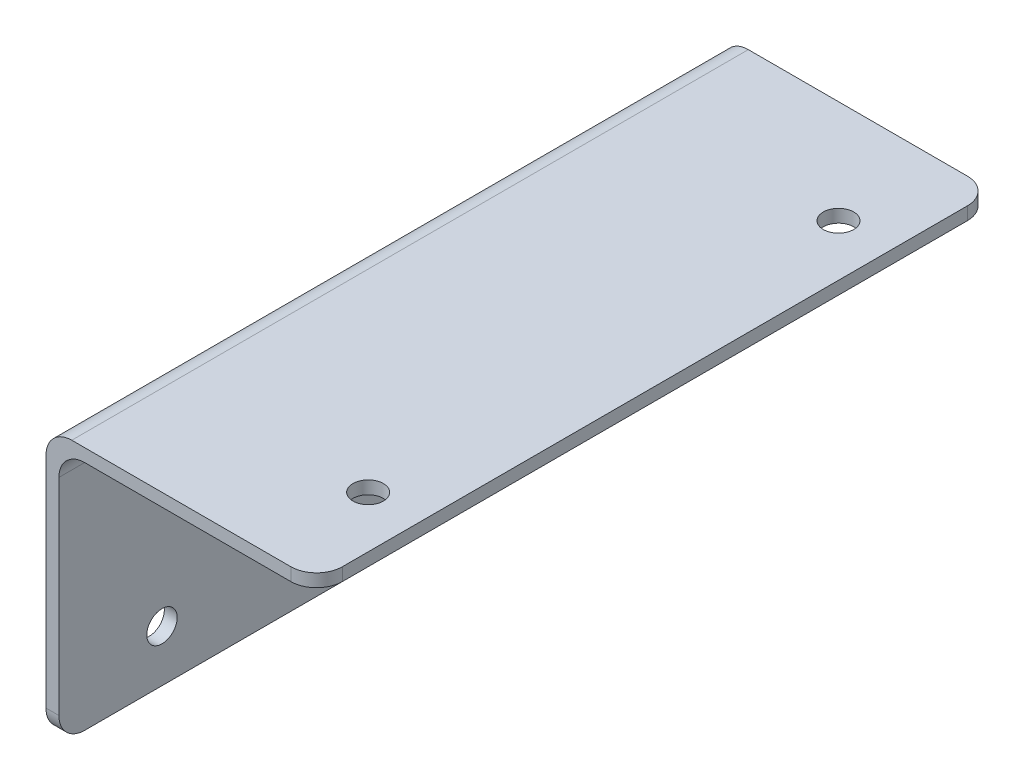
SolidWorks part; units mm, degrees
ref_plane "Front Plane" through (0, 0, 0) normal (0, 0, 1) x (1, 0, 0)
ref_plane "Top Plane" through (0, 0, 0) normal (0, 1, 0) x (1, 0, 0)
ref_plane "Right Plane" through (0, 0, 0) normal (1, 0, 0) x (0, 0, -1)
sketch "Sketch2" plane through (0, 0, 0) normal (0, 0, 1) x (1, 0, 0)
  line L1 (0, 0) -> (-1.27, 0)
  line L2 (0, 0) -> (0, 25.4)
  line L4 (-1.27, 0) -> (-1.27, 26.67)
  line L5 (-1.27, 26.67) -> (25.4, 26.67)
  line L7 (0, 25.4) -> (25.4, 25.4)
  line L8 (25.4, 26.67) -> (25.4, 25.4)
  dimension "D1" = 1.27
  dimension "D2" = 25.4
  dimension "D3" = 1.27
  dimension "D4" = 25.4
extrude "Boss-Extrude1" add sketch "Sketch2" along normal blind 66.675 contours L2 L7 L8 L5 L4 L1
sketch "Sketch3" plane through (-1.27, 0, 0) normal (-1, 0, 0) x (0, 0, 1)
  line L0 (33.3375, 0) -> (33.3375, 31.5293) construction
  line L1 (66.675, 0) -> (0, 0) construction
  circle A0 centre (10.16, 5.08) radius 1.5
  circle A1 centre (56.515, 5.08) radius 1.5
  dimension "D3" = 3
  dimension "D1" = 10.16
  dimension "D2" = 5.08
extrude "Cut-Extrude1" cut sketch "Sketch3" against normal through all
sketch "Sketch6" plane through (0, 26.67, 0) normal (0, 1, 0) x (1, 0, 0)
  line L0 (-1.27, -33.3375) -> (29.2999, -33.3375) construction
  line L1 (-1.27, -66.675) -> (-1.27, 0) construction
  circle A0 centre (20.32, -10.16) radius 1.5
  circle A1 centre (20.32, -56.515) radius 1.5
  dimension "D1" = 5.08
  dimension "D3" = 3
  dimension "D2" = 10.16
extrude "Cut-Extrude2" cut sketch "Sketch6" against normal through all
fillet "Fillet1" radius 2.54 4 edges at (25.4, 26.035, 0) (-0.635, 0, 0) (-0.635, 0, 66.675) (25.4, 26.035, 66.675)
fillet "Fillet2" radius 2.54 2 edges at (0, 25.4, 33.3375) (-1.27, 26.67, 33.3375)
